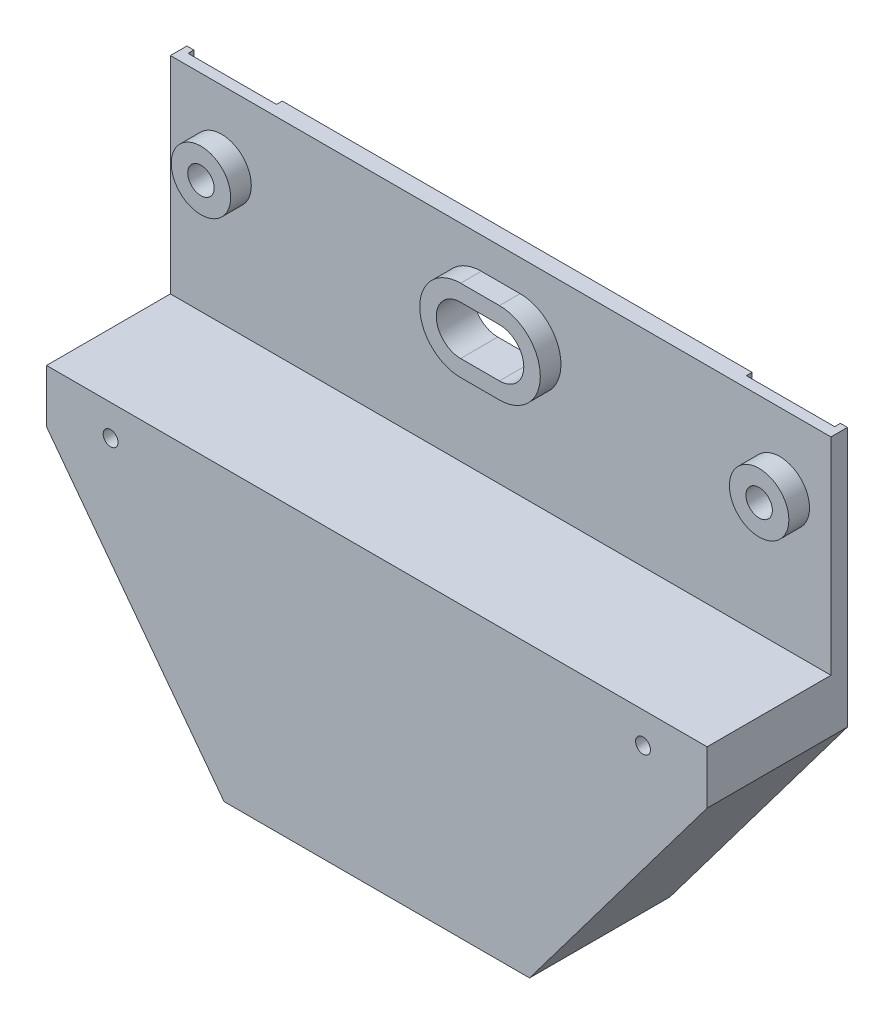
SolidWorks part; units mm, degrees
note: The reader was unsure of these and kept them because the rebuilt part matched: thickness of "Base-Flange1", "Sheet-Metal1", "Sheet-Metal3", "Sheet-Metal4", "Sheet-Metal5", "Sheet-Metal8", "Sheet-Metal9", "Sheet-Metal10", "Sheet-Metal11", "Sheet-Metal12", "Sheet-Metal13", "Sheet-Metal14", "Sheet-Metal15".
ref_plane "Front Plane" through (0, 0, 0) normal (0, 0, 1) x (1, 0, 0)
ref_plane "Top Plane" through (0, 0, 0) normal (0, 1, 0) x (1, 0, 0)
ref_plane "Right Plane" through (0, 0, 0) normal (1, 0, 0) x (0, 0, -1)
sketch "Sketch1" plane through (0, 0, 0) normal (0, 0, 1) x (1, 0, 0)
  line L0 (0, 0) -> (46.99, 0)
  line L1 (46.99, 0) -> (101.6, 72.559)
  line L2 (101.6, 72.559) -> (101.6, 152.4)
  line L3 (101.6, 152.4) -> (-101.6, 152.4)
  line L4 (-101.6, 152.4) -> (-101.6, 72.559)
  line L5 (-101.6, 72.559) -> (-46.99, 0)
  line L6 (-46.99, 0) -> (0, 0)
  point P6 (0, 152.4)
  dimension "D1" = 152.4
  dimension "D2" = 203.2
  dimension "D3" = 93.98
  dimension "D4" = 79.841
base flange "Base-Flange1" sketch "Sketch1" thickness 5.08 reverse thickness direction no parameters "D1"=1
sketch "Sketch6" plane through (0, 0, 0) normal (0, 0, 1) x (1, 0, 0)
  line L0 (-101.6, 72.559) -> (-101.6, 88.9)
  line L1 (101.6, 72.559) -> (46.99, 0)
  line L2 (46.99, 0) -> (101.6, 72.559) construction
  line L3 (46.99, 0) -> (-46.99, 0)
  line L4 (-101.6, 72.559) -> (-46.99, 0) construction
  line L5 (-46.99, 0) -> (-101.6, 72.559)
  line L6 (-101.6, 152.4) -> (-101.6, 72.559) construction
  line L7 (-101.6, 88.9) -> (101.6, 88.9)
  line L8 (101.6, 72.559) -> (101.6, 152.4) construction
  line L9 (101.6, 88.9) -> (101.6, 72.559)
  line L10 (101.6, 152.4) -> (-101.6, 152.4) construction
  dimension "D1" = 63.5
extrude "OG Pocket" add sketch "Sketch6" along normal blind 38.1
sketch "Sketch9" plane through (0, 0, -5.08) normal (0, 0, -1) x (-1, 0, 0)
  line L0 (-76.8896, 44.5893) -> (-76.8896, 85.725)
  line L1 (-76.8896, 85.725) -> (76.8896, 85.725)
  line L2 (76.8896, 85.725) -> (76.8896, 44.5893)
  line L3 (76.8896, 44.5893) -> (45.72, 3.175)
  line L4 (45.72, 3.175) -> (-45.72, 3.175)
  line L5 (-45.72, 3.175) -> (-76.8896, 44.5893)
  line L6 (101.6, 72.559) -> (46.99, 0) construction
  line L7 (-46.99, 0) -> (-101.6, 72.559) construction
  line L8 (-101.6, 88.9) -> (101.6, 88.9) construction
  line L9 (-101.6, 88.9) -> (101.6, 88.9) construction
  line L10 (46.99, 0) -> (-46.99, 0) construction
  line L11 (46.99, 0) -> (-46.99, 0) construction
  point P2 (0, 85.725)
  point P7 (0, 3.175)
  dimension "D1" = 91.44
  dimension "D2" = 3.175
  dimension "D3" = 3.175
extrude "Shell of Pocket" cut sketch "Sketch9" against normal blind 38.1 normal cut yes
sketch "Sketch10" plane through (0, 0, -5.08) normal (0, 0, -1) x (-1, 0, 0)
  line L0 (-5.969, 137.668) -> (5.969, 137.668)
  line L1 (5.969, 122.682) -> (-5.969, 122.682)
  line L2 (-101.6, 152.4) -> (101.6, 152.4) construction
  arc A0 (5.969, 137.668) -> (5.969, 122.682) centre (5.969, 130.175) cw
  arc A1 (-5.969, 122.682) -> (-5.969, 137.668) centre (-5.969, 130.175) cw
  point P5 (-13.462, 130.175)
  point P7 (13.462, 130.175)
  point P8 (0, 137.668)
  point P11 (0, 152.4)
  dimension "D1" = 26.924
  dimension "D2" = 14.986
  dimension "D3" = 14.732
extrude "Battery Tail Hole" cut sketch "Sketch10" against normal through all and the other way through all normal cut yes
sketch "Sketch11" plane through (0, 0, -5.08) normal (0, 0, -1) x (-1, 0, 0)
  circle A0 centre (-85.852, 130.175) radius 4.064
  arc A1 (-5.969, 137.668) -> (-5.969, 122.682) centre (-5.969, 130.175) ccw construction
  circle A2 centre (85.852, 130.175) radius 4.064
  arc A3 (5.969, 122.682) -> (5.969, 137.668) centre (5.969, 130.175) ccw construction
  point P6 (-13.462, 130.175)
  point P14 (13.462, 130.175)
  dimension "D1" = 72.39
  dimension "D2" = 72.39
extrude "Tab Bolt Holes" cut sketch "Sketch11" against normal through all normal cut yes
sketch "Sketch12" plane through (76.8896, 0, 0) normal (-1, 0, 0) x (0, 0, 1)
  line L1 (33.02, 85.725) -> (2.54, 85.725)
  line L2 (33.02, 85.725) -> (33.02, 73.0081)
  line L3 (33.02, 73.0081) -> (2.54, 73.0081)
  line L4 (2.54, 85.725) -> (2.54, 73.0081)
  dimension "D1" = 30.48
  dimension "D2" = 12.7169
extrude "Weight Saver" cut sketch "Sketch12" against normal blind 10.16 normal cut yes
mirror "Mirror1" about plane through (0, 0, 0) normal (1, 0, 0) of "Weight Saver"
sketch "Sketch13" plane through (0, 0, -5.08) normal (0, 0, -1) x (-1, 0, 0)
  line L0 (-87.0496, 73.0081) -> (-87.0496, 85.725) construction
  circle A0 centre (-81.8854, 79.3665) radius 2.286
  point P8 (-87.0496, 79.3665)
extrude "Bolt holes- Through" cut sketch "Sketch13" against normal through all both and the other way through all normal cut yes
mirror "Mirror2" about plane through (0, 0, 0) normal (1, 0, 0) of "Bolt holes- Through"
sketch "Sketch14" plane through (0, 0, -5.08) normal (0, 0, -1) x (-1, 0, 0)
  line L0 (72.263, 152.4) -> (72.263, 130.175)
  line L1 (-101.6, 152.4) -> (101.6, 152.4) construction
  line L2 (99.441, 130.175) -> (99.441, 152.4)
  line L3 (99.441, 152.4) -> (72.263, 152.4)
  arc A0 (72.263, 130.175) -> (99.441, 130.175) centre (85.852, 130.175) ccw
  circle A2 centre (85.852, 130.175) radius 4.064 construction
  dimension "D1" = 27.178
extrude "Cut-Extrude6" cut sketch "Sketch14" against normal blind 1.778 normal cut yes
mirror "Mirror3" about plane through (0, 0, 0) normal (1, 0, 0) of "Cut-Extrude6"
sketch "Sketch15" plane through (0, 0, 38.1) normal (0, 0, 1) x (1, 0, 0)
  circle A0 centre (0, 44.0015) radius 38.1
sketch "Possible Lip" plane through (0, 0, 0) normal (0, 0, 1) x (1, 0, 0)
  line L0 (-5.969, 122.682) -> (5.969, 122.682) construction
  line L1 (5.969, 137.668) -> (-5.969, 137.668) construction
  line L2 (-5.969, 122.682) -> (5.969, 122.682)
  line L3 (5.969, 137.668) -> (-5.969, 137.668)
  line L4 (-5.969, 117.602) -> (5.969, 117.602)
  line L5 (5.969, 142.748) -> (-5.969, 142.748)
  arc A0 (-5.969, 137.668) -> (-5.969, 122.682) centre (-5.969, 130.175) ccw construction
  arc A1 (5.969, 122.682) -> (5.969, 137.668) centre (5.969, 130.175) ccw construction
  arc A2 (-5.969, 137.668) -> (-5.969, 122.682) centre (-5.969, 130.175) ccw
  arc A3 (5.969, 122.682) -> (5.969, 137.668) centre (5.969, 130.175) ccw
  arc A4 (5.969, 117.602) -> (5.969, 142.748) centre (5.969, 130.175) ccw
  arc A5 (-5.969, 142.748) -> (-5.969, 117.602) centre (-5.969, 130.175) ccw
  circle A6 centre (-85.852, 130.175) radius 4.064 construction
  circle A7 centre (85.852, 130.175) radius 4.064 construction
  circle A8 centre (-85.852, 130.175) radius 4.064
  circle A9 centre (85.852, 130.175) radius 4.064
  circle A10 centre (85.852, 130.175) radius 9.144
  circle A11 centre (-85.852, 130.175) radius 9.144
  dimension "D1" = 5.08
  dimension "D2" = 5.08
  dimension "D3" = 5.08
extrude "Battery Lip" add sketch "Possible Lip" along normal blind 6.35
sketch "Bend-Lines1" [suppressed] plane through (0, 0, 0) normal (0, 1, 0) x (1, 0, 0)
sketch "Bounding-Box1" [suppressed] plane through (0, 0, 0) normal (0, 1, 0) x (1, 0, 0)
sheet metal parameters "Sheet-Metal1" thickness 5.08 parameters "D1"=1
flat pattern "Flat-Pattern1" [suppressed]
sketch "Bend-Lines2" plane through (0, 0, 0) normal (0, 1, 0) x (1, 0, 0)
sketch3d "Bounding-Box2" [suppressed]
  line L0 (-101.6, 0, 0) -> (101.6, 0, 0) construction
  line L1 (-101.6, 152.4, 0) -> (101.6, 152.4, 0) construction
  line L2 (-101.6, 0, 0) -> (-101.6, 152.4, 0) construction
  line L3 (101.6, 0, 0) -> (101.6, 152.4, 0) construction
sheet metal parameters "Sheet-Metal3" thickness 5.08 parameters "D1"=1, "D7"=6.35
flat pattern "Flat-Pattern1"
sketch "Bend-Lines2" plane through (0, 0, 0) normal (0, 1, 0) x (1, 0, 0)
sketch3d "Bounding-Box2" [suppressed]
  line L0 (-101.6, 88.9, 0) -> (101.6, 88.9, 0) construction
  line L1 (-101.6, 152.4, 0) -> (101.6, 152.4, 0) construction
  line L2 (-101.6, 88.9, 0) -> (-101.6, 152.4, 0) construction
  line L3 (101.6, 88.9, 0) -> (101.6, 152.4, 0) construction
sheet metal parameters "Sheet-Metal4" thickness 5.08 parameters "D1"=1, "D7"=6.35
flat pattern "Flat-Pattern1"
sketch "Bend-Lines2" plane through (0, 0, 0) normal (0, 1, 0) x (1, 0, 0)
sketch3d "Bounding-Box2" [suppressed]
  line L0 (-101.6, 88.9, 0) -> (101.6, 88.9, 0) construction
  line L1 (-101.6, 152.4, 0) -> (101.6, 152.4, 0) construction
  line L2 (-101.6, 88.9, 0) -> (-101.6, 152.4, 0) construction
  line L3 (101.6, 88.9, 0) -> (101.6, 152.4, 0) construction
sheet metal parameters "Sheet-Metal5" thickness 5.08 parameters "D1"=1, "D7"=6.35
flat pattern "Flat-Pattern1"
sketch "Bend-Lines2" plane through (0, 0, 0) normal (0, 1, 0) x (1, 0, 0)
sketch3d "Bounding-Box2" [suppressed]
  line L0 (-101.6, 88.9, 0) -> (101.6, 88.9, 0) construction
  line L1 (-101.6, 152.4, 0) -> (101.6, 152.4, 0) construction
  line L2 (-101.6, 88.9, 0) -> (-101.6, 152.4, 0) construction
  line L3 (101.6, 88.9, 0) -> (101.6, 152.4, 0) construction
sheet metal parameters "Sheet-Metal8" thickness 5.08 parameters "D1"=1, "D7"=6.35
flat pattern "Flat-Pattern1"
sketch "Bend-Lines2" plane through (0, 0, 0) normal (0, 1, 0) x (1, 0, 0)
sketch3d "Bounding-Box2" [suppressed]
  line L0 (-101.6, 88.9, 0) -> (101.6, 88.9, 0) construction
  line L1 (-101.6, 152.4, 0) -> (101.6, 152.4, 0) construction
  line L2 (-101.6, 88.9, 0) -> (-101.6, 152.4, 0) construction
  line L3 (101.6, 88.9, 0) -> (101.6, 152.4, 0) construction
sheet metal parameters "Sheet-Metal9" thickness 5.08 parameters "D1"=1, "D7"=6.35
flat pattern "Flat-Pattern1"
sketch "Bend-Lines2" plane through (0, 0, 0) normal (0, 1, 0) x (1, 0, 0)
sketch3d "Bounding-Box2" [suppressed]
  line L0 (-101.6, 88.9, 0) -> (101.6, 88.9, 0) construction
  line L1 (-101.6, 152.4, 0) -> (101.6, 152.4, 0) construction
  line L2 (-101.6, 88.9, 0) -> (-101.6, 152.4, 0) construction
  line L3 (101.6, 88.9, 0) -> (101.6, 152.4, 0) construction
sheet metal parameters "Sheet-Metal10" thickness 5.08 parameters "D1"=1, "D7"=6.35
flat pattern "Flat-Pattern1"
sketch "Bend-Lines2" plane through (0, 0, 0) normal (0, 1, 0) x (1, 0, 0)
sketch3d "Bounding-Box2" [suppressed]
  line L0 (-101.6, 88.9, 0) -> (101.6, 88.9, 0) construction
  line L1 (-101.6, 152.4, 0) -> (101.6, 152.4, 0) construction
  line L2 (-101.6, 88.9, 0) -> (-101.6, 152.4, 0) construction
  line L3 (101.6, 88.9, 0) -> (101.6, 152.4, 0) construction
sheet metal parameters "Sheet-Metal11" thickness 5.08 parameters "D1"=1, "D7"=6.35
flat pattern "Flat-Pattern1"
sketch "Bend-Lines2" plane through (0, 0, 0) normal (0, 1, 0) x (1, 0, 0)
sketch3d "Bounding-Box2" [suppressed]
  line L0 (-101.6, 88.9, 0) -> (101.6, 88.9, 0) construction
  line L1 (-101.6, 152.4, 0) -> (101.6, 152.4, 0) construction
  line L2 (-101.6, 88.9, 0) -> (-101.6, 152.4, 0) construction
  line L3 (101.6, 88.9, 0) -> (101.6, 152.4, 0) construction
sheet metal parameters "Sheet-Metal12" thickness 5.08 parameters "D1"=1, "D7"=6.35
flat pattern "Flat-Pattern1"
sketch "Bend-Lines2" plane through (0, 0, 0) normal (0, 1, 0) x (1, 0, 0)
sketch3d "Bounding-Box2" [suppressed]
  line L0 (-101.6, 88.9, 0) -> (101.6, 88.9, 0) construction
  line L1 (-101.6, 152.4, 0) -> (101.6, 152.4, 0) construction
  line L2 (-101.6, 88.9, 0) -> (-101.6, 152.4, 0) construction
  line L3 (101.6, 88.9, 0) -> (101.6, 152.4, 0) construction
sheet metal parameters "Sheet-Metal13" thickness 5.08 parameters "D1"=1, "D7"=6.35
flat pattern "Flat-Pattern1"
sketch "Bend-Lines2" plane through (0, 0, 0) normal (0, 1, 0) x (1, 0, 0)
sketch3d "Bounding-Box2" [suppressed]
  line L0 (-101.6, 88.9, 0) -> (101.6, 88.9, 0) construction
  line L1 (-101.6, 152.4, 0) -> (101.6, 152.4, 0) construction
  line L2 (-101.6, 88.9, 0) -> (-101.6, 152.4, 0) construction
  line L3 (101.6, 88.9, 0) -> (101.6, 152.4, 0) construction
sheet metal parameters "Sheet-Metal14" thickness 5.08 parameters "D1"=1, "D7"=6.35
flat pattern "Flat-Pattern1"
sketch "Bend-Lines2" plane through (0, 0, 0) normal (0, 1, 0) x (1, 0, 0)
sketch3d "Bounding-Box2" [suppressed]
  line L0 (-101.6, 88.9, 0) -> (101.6, 88.9, 0) construction
  line L1 (-101.6, 152.4, 0) -> (101.6, 152.4, 0) construction
  line L2 (-101.6, 88.9, 0) -> (-101.6, 152.4, 0) construction
  line L3 (101.6, 88.9, 0) -> (101.6, 152.4, 0) construction
sheet metal parameters "Sheet-Metal15" thickness 5.08 parameters "D1"=1, "D7"=6.35
flat pattern "Flat-Pattern1"
sketch "Bend-Lines2" plane through (0, 0, 0) normal (0, 1, 0) x (1, 0, 0)
sketch3d "Bounding-Box2" [suppressed]
  line L0 (-101.6, 88.9, 0) -> (101.6, 88.9, 0) construction
  line L1 (-101.6, 152.4, 0) -> (101.6, 152.4, 0) construction
  line L2 (-101.6, 88.9, 0) -> (-101.6, 152.4, 0) construction
  line L3 (101.6, 88.9, 0) -> (101.6, 152.4, 0) construction
